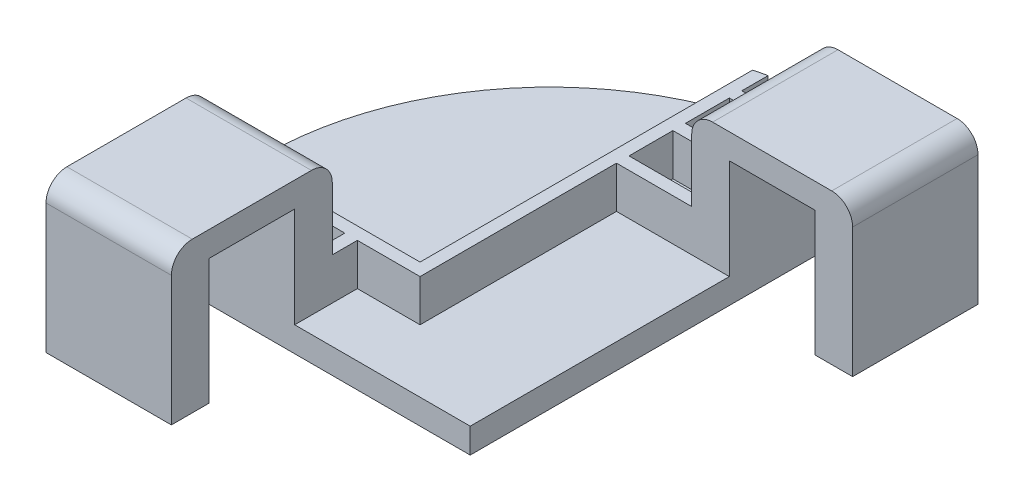
SolidWorks part; units mm, degrees
ref_plane "Front Plane" through (0, 0, 0) normal (0, 0, 1) x (1, 0, 0)
ref_plane "Top Plane" through (0, 0, 0) normal (0, 1, 0) x (1, 0, 0)
ref_plane "Right Plane" through (0, 0, 0) normal (1, 0, 0) x (0, 0, -1)
sketch "Sketch1" plane through (0, 0, 0) normal (0, 1, 0) x (1, 0, 0)
  line L0 (-72, 0) -> (-72, -20.5)
  line L1 (-42, 9) -> (-72, 9)
  line L2 (-42, 9) -> (-42, 0)
  line L3 (-42, 0) -> (-72, 0)
  line L4 (-72, 9) -> (-72, 0)
  line L5 (-9, 92) -> (0, 92)
  line L6 (-9, 92) -> (-9, 62)
  line L7 (-9, 62) -> (0, 62)
  line L8 (0, 92) -> (0, 62)
  line L9 (-72, -20.5) -> (-42, -20.5)
  line L10 (-72, -20.5) -> (-72, -29.5)
  line L11 (-72, -29.5) -> (-42, -29.5)
  line L12 (-42, -20.5) -> (-42, -29.5)
  line L13 (20.5, 92) -> (29.5, 92)
  line L14 (20.5, 92) -> (20.5, 62)
  line L15 (20.5, 62) -> (29.5, 62)
  line L16 (29.5, 92) -> (29.5, 62)
  line L17 (-42, 0) -> (-42, -20.5)
  line L18 (0, 62) -> (20.5, 62)
  line L19 (0, 92) -> (20.5, 92)
  line L20 (0, 99.8961) -> (0, 92)
  line L21 (0, 62) -> (0, 0)
  line L22 (-72, 0) -> (-80.7745, 0)
  line L23 (0, 99.8961) -> (-12.2463, 99.8961)
  line L24 (0, 0) -> (-42, 0)
  line L25 (-80.7745, 0) -> (-80.7745, 31.3679)
  arc A0 (-12.2463, 99.8961) -> (-80.7745, 31.3679) centre (-12.2463, 31.3679) ccw
  dimension "D1" = 62
  dimension "D2" = 42
  dimension "D3" = 20.5
  dimension "D4" = 30
  dimension "D5" = 9
  dimension "D6" = 9
extrude "Boss-Extrude1" add sketch "Sketch1" along normal blind 6 contours L1 L4 L3 L2 | L8 L5 L6 L7 | L23 A0 L25 L22 L4 L1 L2 L24 L21 L7 L6 L5 L20 region at (-57, 0, -4.5) region at (-37.3094, 0, -45.3563) region at (-4.5, 0, -77)
extrude "Boss-Extrude2" add sketch "Sketch1<3>" along normal blind 24 from surface contours L1 L4 L3 L2 | L8 L5 L6 L7 region at (-57, 0, -4.5) region at (-4.5, 0, -77) starting at face at (-37.5976, 6, -49.0706)
sketch "Sketch1<3>" plane through (0, 0, 0) normal (0, 1, 0) x (1, 0, 0) same geometry as "Sketch1"
extrude "Boss-Extrude3" add sketch "Sketch1<4>" along normal blind 6 from surface contours L1 L4 L3 L2 | L17 L3 L0 L9 | L12 L9 L10 L11 | L8 L5 L6 L7 | L19 L8 L18 L14 | L16 L13 L14 L15 region at (-57, 0, 10.25) region at (-57, 0, -4.5) region at (-57, 0, 25) region at (-4.5, 0, -77) region at (10.25, 0, -77) region at (25, 0, -77) starting at face at (-57, 30, -4.5)
sketch "Sketch1<4>" plane through (0, 0, 0) normal (0, 1, 0) x (1, 0, 0) same geometry as "Sketch1"
extrude "Boss-Extrude4" add sketch "Sketch1<5>" against normal up to surface from surface contours L12 L9 L10 L11 | L16 L13 L14 L15 region at (-57, 0, 25) region at (25, 0, -77) up to face at (-37.5976, 0, -49.0706) starting at face at (-57, 30, 14.75)
sketch "Sketch1<5>" plane through (0, 0, 0) normal (0, 1, 0) x (1, 0, 0) same geometry as "Sketch1"
sketch "Sketch2" plane through (0, 6, 0) normal (0, 1, 0) x (1, 0, 0)
  line L0 (-27, 109.8961) -> (-27, 15)
  line L1 (-27, 15) -> (-90.7745, 15)
  line L2 (-90.7745, 15) -> (-90.7745, 18)
  line L3 (-90.7745, 18) -> (-30, 18)
  line L4 (-30, 18) -> (-30, 109.8961)
  line L5 (-30, 109.8961) -> (-27, 109.8961)
  line L7 (0, 0) -> (-42, 0) construction
  line L8 (-27, 75.5) -> (-9, 75.5)
  line L9 (-9, 75.5) -> (-9, 78.5)
  line L10 (-9, 78.5) -> (-27, 78.5)
  line L11 (-9, 92) -> (-9, 62) construction
  line L12 (-58.5, 15) -> (-58.5, 9)
  line L13 (-58.5, 9) -> (-55.5, 9)
  line L14 (-55.5, 9) -> (-55.5, 15)
  line L15 (-42, 9) -> (-72, 9) construction
  line L16 (-42, 9) -> (-42, 15)
  line L17 (-42, 9) -> (-45, 9)
  line L18 (-45, 9) -> (-45, 15)
  line L19 (-72, 9) -> (-72, 15)
  line L20 (-72, 9) -> (-69, 9)
  line L21 (-72, 9) -> (-42, 9) construction
  line L22 (-69, 9) -> (-69, 15)
  line L23 (-9, 62) -> (-27, 62)
  line L24 (-9, 62) -> (-9, 65)
  line L25 (-9, 65) -> (-27, 65)
  line L26 (-9, 92) -> (-27, 92)
  line L27 (-9, 92) -> (-9, 89)
  line L28 (-9, 62) -> (-9, 92) construction
  line L29 (-9, 89) -> (-27, 89)
  line L30 (0, 62) -> (0, 0) construction
  point P16 (-9, 77)
  point P19 (-9, 77)
  point P24 (-57, 9)
  point P27 (-57, 9)
  line M8 (-9, 62) -> (-9, 92)
  arc M12 (-12.2463, 99.8961) -> (-80.7745, 31.3679) centre (-12.2463, 31.3679) ccw
  line M13 (-80.7745, 31.3679) -> (-80.7745, 0)
  line M16 (-72, 9) -> (-42, 9)
  dimension "D1" = 3
  dimension "D3" = 15
  dimension "D4" = 10
  dimension "D5" = 10
  dimension "D6" = 3
  dimension "D2" = 30
extrude "Boss-Extrude5" add sketch "Sketch2" along normal blind 10 contours L4 L3 L1 L0 M13 M12 | L14 L1 L12 M16 | L10 L0 L8 M8 | L22 L1 L19 M16 | L18 L16 L1 M16 | L25 L0 L23 M8 | L29 L26 L0 M8 region at (-18, 6, -90.5) region at (-27.9914, 6, -90.5) region at (-18, 6, -77) region at (-18, 6, -63.5) region at (-70.5, 6, -12) region at (-43.5, 6, -12) region at (-57, 6, -12)
fillet "Fillet1" radius 5 4 edges at (29.5, 36, -77) (-9, 36, -77) (-57, 36, 29.5) (-57, 36, -9)
equation "\"D5@Sketch2\"=\"D4@Sketch2\""
